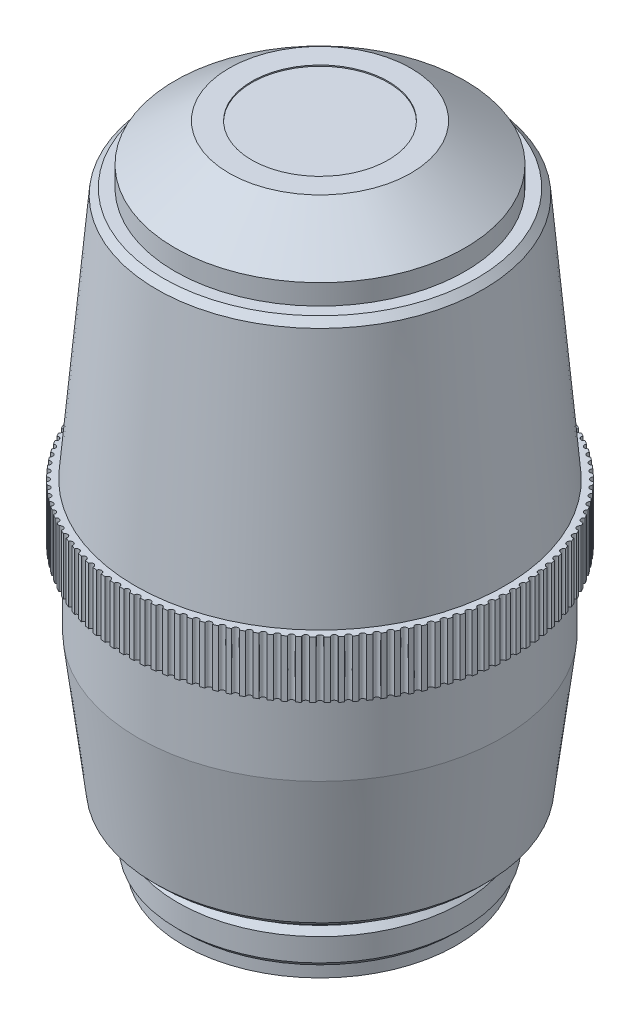
SolidWorks part; units mm, degrees
ref_plane "Front Plane" through (0, 0, 0) normal (0, 0, 1) x (1, 0, 0)
ref_plane "Top Plane" through (0, 0, 0) normal (0, 1, 0) x (1, 0, 0)
ref_plane "Right Plane" through (0, 0, 0) normal (1, 0, 0) x (0, 0, -1)
sketch "Sketch1" plane through (0, 0, 0) normal (1, 0, 0) x (0, 0, -1)
  line L0 (0, 40) -> (0, -40) construction
  line L1 (0, 28.405) -> (0, -28.405)
  line L2 (0, -28.405) -> (-12, -28.405)
  line L3 (-12, -28.405) -> (-12, -27.405)
  line L4 (-12, -27.405) -> (-12.5, -26.905)
  line L5 (-12.5, -26.905) -> (-12.5, -24.905)
  line L6 (-12.5, -24.905) -> (-12, -24.405)
  line L7 (-12, -24.405) -> (-12, -23.405)
  line L8 (-12, -23.405) -> (-13.3011, -23.405)
  line L9 (-13.3011, -23.405) -> (-13.5511, -23.155)
  line L10 (-13.5511, -23.155) -> (-13.5511, -22.905)
  line L11 (-13.5511, -22.905) -> (-14.0511, -22.905)
  line L12 (-14.0511, -22.905) -> (-14.5511, -22.405)
  line L13 (-14.5511, -22.405) -> (-16, -10.605)
  line L14 (-16, -10.605) -> (-16, -3.905)
  line L15 (-16, -3.905) -> (-17, -3.905)
  line L16 (-17, -3.905) -> (-17, 1.095)
  line L17 (-17, 1.095) -> (-16.25, 1.095)
  line L18 (-16.25, 1.095) -> (-14.3572, 22.7293)
  line L19 (-14.3572, 22.7293) -> (-13.7916, 23.295)
  line L20 (-13.7916, 23.295) -> (-12.75, 23.295)
  line L21 (-12.75, 23.295) -> (-12.75, 25.079)
  line L22 (-12.75, 25.079) -> (-8, 28.405)
  line L23 (-8, 28.405) -> (0, 28.405)
  point P2 (0, 0)
  point P6 (0, 0)
  dimension "D1" = 80
  dimension "D2" = 56.81
  dimension "D3" = 16
  dimension "D4" = 25.5
  dimension "D5" = 35
  dimension "D6" = 5.11
  dimension "D7" = 45
  dimension "D8" = 0.8
  dimension "D9" = 5
  dimension "D10" = 22.2
  dimension "D11" = 34
  dimension "D12" = 32.5
  dimension "D13" = 32
  dimension "D14" = 25
  dimension "D15" = 5
  dimension "D16" = 1
  dimension "D17" = 1
  dimension "D18" = 45
  dimension "D19" = 0.5
  dimension "D20" = 12.8
  dimension "D21" = 7
  dimension "D22" = 0.25
  dimension "D23" = 0.25
  dimension "D24" = 45
  dimension "D25" = 0.5
  dimension "D26" = 0.5
  dimension "D27" = 5
revolve "Revolve1" add sketch "Sketch1" angle 360 about L0
cosmetic thread "Cosmetic Thread1" parameters "D2"=24
sketch "Sketch2" plane through (0, -28.405, 0) normal (0, -1, 0) x (-1, 0, 0)
  circle A0 centre (0, 0) radius 4.5
  dimension "D1" = 9
extrude "Cut-Extrude1" cut sketch "Sketch2" against normal blind 3
ref_plane "WD" through (0, 35.305, 0) normal (0, 1, 0) x (1, 0, 0)
ref_plane "Plane2" through (0, 1.095, 0) normal (0, 1, 0) x (1, 0, 0)
ref_axis "Axis1" through (0, 1.095, -15.459) along (0, 0, -1)
sketch "Sketch3" plane through (0, 1.095, 0) normal (0, 1, 0) x (1, 0, 0)
  line L0 (0, 15.459) -> (0, 18.7) construction
  arc A0 (0.25, 16.9982) -> (-0.25, 16.9982) centre (0, 17) cw
  circle A2 centre (0, 0) radius 17 construction
  dimension "D1" = 0.25
extrude "Cut-Extrude2" cut sketch "Sketch3" against normal through all and the other way through all flip side to cut
pattern_circular "CirPattern1" count 120 every 3 about axis through (0, 40, 0) along (0, 1, 0) of "Cut-Extrude2"
sketch "Sketch4" plane through (0, 28.405, 0) normal (0, 1, 0) x (1, 0, 0)
  circle A0 centre (0, 0) radius 6
  dimension "D1" = 12
extrude "Cut-Extrude3" cut sketch "Sketch4" against normal blind 0.1
ref_axis "Axis2" through (8.8309, 35.305, 0) along (-1, 0, 0)
ref_axis "Axis3" through (0, 35.305, 8.8) along (0, 0, -1)
sketch "Sketch5" plane through (0, 35.305, 0) normal (0, 1, 0) x (1, 0, 0)
  line L1 (-0.128, 0.55) -> (0.128, 0.55) construction
  line L2 (-0.128, 0.55) -> (-0.128, -0.55) construction
  line L3 (-0.128, -0.55) -> (0.128, -0.55) construction
  line L4 (0.128, 0.55) -> (0.128, -0.55) construction
  line L5 (-0.128, 0.55) -> (0.128, -0.55) construction
  line L6 (-0.128, -0.55) -> (0.128, 0.55) construction
  point P0 (0, 0)
  dimension "D1" = 1.1
  dimension "D2" = 0.256
ref_axis "Axis4" through (0.128, 35.305, -0.55) along (0, 0, 1)
ref_axis "Axis5" through (-0.128, 35.305, -0.55) along (0, 0, 1)
